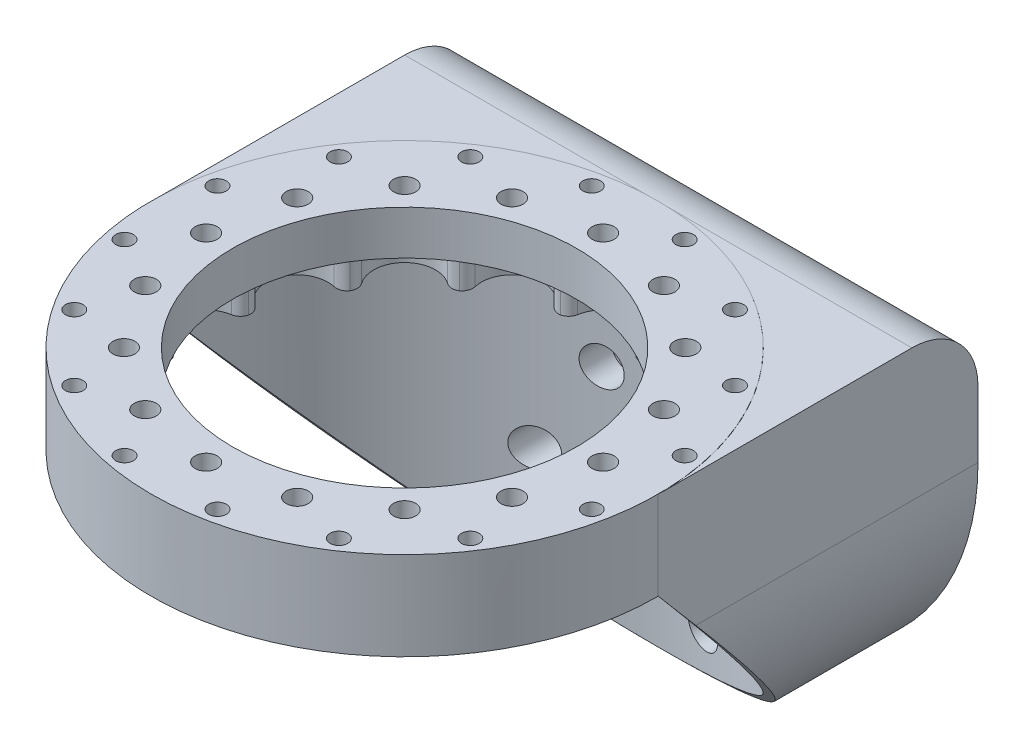
SolidWorks part; units mm, degrees
ref_plane "Front Plane" through (0, 0, 0) normal (0, 0, 1) x (1, 0, 0)
ref_plane "Top Plane" through (0, 0, 0) normal (0, 1, 0) x (1, 0, 0)
ref_plane "Right Plane" through (0, 0, 0) normal (1, 0, 0) x (0, 0, -1)
sketch "Sketch1" plane through (0, 0, 0) normal (0, 1, 0) x (1, 0, 0)
  line L0 (-10.5349, 52.9624) -> (0, 0) construction
  line L1 (0, 0) -> (24.6214, 0) construction
  circle A12 centre (0, 0) radius 39
  circle A13 centre (0, 0) radius 57.5
  circle A14 centre (0, 0) radius 54 construction
  circle A15 centre (-10.5349, 52.9624) radius 2
  circle A16 centre (10.5349, 52.9624) radius 2
  circle A17 centre (30.0008, 44.8994) radius 2
  circle A18 centre (44.8994, 30.0008) radius 2
  circle A19 centre (52.9624, 10.5349) radius 2
  circle A20 centre (52.9624, -10.5349) radius 2
  circle A21 centre (44.8994, -30.0008) radius 2
  circle A22 centre (30.0008, -44.8994) radius 2
  circle A23 centre (10.5349, -52.9624) radius 2
  circle A24 centre (-10.5349, -52.9624) radius 2
  circle A25 centre (-30.0008, -44.8994) radius 2
  circle A26 centre (-44.8994, -30.0008) radius 2
  circle A47 centre (-52.9624, -10.5349) radius 2
  circle A48 centre (-52.9624, 10.5349) radius 2
  circle A49 centre (-44.8994, 30.0008) radius 2
  circle A50 centre (-30.0008, 44.8994) radius 2
  point P21 (0, 0)
  point P28 (0, 0)
  point P56 (0, 0)
  point P60 (0, 0)
  dimension "D1" = 101.25
  dimension "D4" = 115
  dimension "D5" = 78
  dimension "D6" = 108
  dimension "D7" = 4
  dimension "D8" = 16
extrude "Boss-Extrude1" add sketch "Sketch1" along normal blind 10
sketch "Sketch2" plane through (0, 10, 0) normal (0, 1, 0) x (1, 0, 0)
  circle A0 centre (0, 0) radius 45 construction
  circle A1 centre (0, 45) radius 2.5
  circle A2 centre (17.2208, 41.5746) radius 2.5
  circle A3 centre (31.8198, 31.8198) radius 2.5
  circle A4 centre (41.5746, 17.2208) radius 2.5
  circle A5 centre (45, 0) radius 2.5
  circle A6 centre (41.5746, -17.2208) radius 2.5
  circle A7 centre (31.8198, -31.8198) radius 2.5
  circle A8 centre (17.2208, -41.5746) radius 2.5
  circle A9 centre (0, -45) radius 2.5
  circle A10 centre (-17.2208, -41.5746) radius 2.5
  circle A11 centre (-31.8198, -31.8198) radius 2.5
  circle A12 centre (-41.5746, -17.2208) radius 2.5
  circle A13 centre (-45, 0) radius 2.5
  circle A14 centre (-41.5746, 17.2208) radius 2.5
  circle A15 centre (-31.8198, 31.8198) radius 2.5
  circle A16 centre (-17.2208, 41.5746) radius 2.5
  point P27 (0, 0)
  dimension "D1" = 90
  dimension "D2" = 5
  dimension "D3" = 16
extrude "Cut-Extrude1" cut sketch "Sketch2" against normal blind 10
sketch "Sketch4" plane through (0, 0, 0) normal (0, 1, 0) x (1, 0, 0)
  circle A0 centre (0, 0) radius 45 construction
  circle A1 centre (0, 45) radius 5
  circle A2 centre (0, 45) radius 2.5
  circle A3 centre (17.2208, 41.5746) radius 2.5
  circle A4 centre (31.8198, 31.8198) radius 2.5
  circle A5 centre (41.5746, 17.2208) radius 2.5
  circle A6 centre (45, 0) radius 2.5
  circle A7 centre (41.5746, -17.2208) radius 2.5
  circle A8 centre (31.8198, -31.8198) radius 2.5
  circle A9 centre (17.2208, -41.5746) radius 2.5
  circle A10 centre (0, -45) radius 2.5
  circle A11 centre (-17.2208, -41.5746) radius 2.5
  circle A12 centre (-31.8198, -31.8198) radius 2.5
  circle A13 centre (17.2208, 41.5746) radius 5
  circle A14 centre (31.8198, 31.8198) radius 5
  circle A15 centre (41.5746, 17.2208) radius 5
  circle A16 centre (45, 0) radius 5
  circle A17 centre (41.5746, -17.2208) radius 5
  circle A18 centre (31.8198, -31.8198) radius 5
  circle A19 centre (17.2208, -41.5746) radius 5
  circle A20 centre (0, -45) radius 5
  circle A21 centre (-17.2208, -41.5746) radius 5
  circle A22 centre (-31.8198, -31.8198) radius 5
  circle A23 centre (-41.5746, -17.2208) radius 5
  circle A24 centre (-45, 0) radius 5
  circle A25 centre (-41.5746, 17.2208) radius 5
  circle A26 centre (-31.8198, 31.8198) radius 5
  circle A27 centre (-17.2208, 41.5746) radius 5
  circle A28 centre (-41.5746, -17.2208) radius 2.5
  circle A29 centre (-45, 0) radius 2.5
  circle A30 centre (-41.5746, 17.2208) radius 2.5
  circle A31 centre (-31.8198, 31.8198) radius 2.5
  circle A32 centre (-17.2208, 41.5746) radius 2.5
  point P29 (0, 0)
  point P50 (0, 0)
  dimension "D1" = 10
  dimension "D2" = 16
  dimension "D3" = 16
extrude "Boss-Extrude3" add sketch "Sketch4" against normal blind 0.4
sketch "Sketch5" plane through (0, 0, 0) normal (0, -1, 0) x (1, 0, 0)
  circle A0 centre (0, 0) radius 57.5
  circle A1 centre (0, 0) radius 45
  circle A2 centre (0, 45) radius 7
  circle A3 centre (17.2208, 41.5746) radius 7
  circle A4 centre (31.8198, 31.8198) radius 7
  circle A5 centre (41.5746, 17.2208) radius 7
  circle A6 centre (45, 0) radius 7
  circle A7 centre (41.5746, -17.2208) radius 7
  circle A8 centre (31.8198, -31.8198) radius 7
  circle A9 centre (17.2208, -41.5746) radius 7
  circle A10 centre (0, -45) radius 7
  circle A11 centre (-17.2208, -41.5746) radius 7
  circle A12 centre (-31.8198, -31.8198) radius 7
  circle A13 centre (-41.5746, -17.2208) radius 7
  circle A14 centre (-45, 0) radius 7
  circle A15 centre (-41.5746, 17.2208) radius 7
  circle A16 centre (-31.8198, 31.8198) radius 7
  circle A17 centre (-17.2208, 41.5746) radius 7
  circle A18 centre (0, 0) radius 54 construction
  circle A19 centre (-10.5349, 52.9624) radius 2
  circle A20 centre (10.5349, 52.9624) radius 2
  circle A21 centre (30.0008, 44.8994) radius 2
  circle A22 centre (44.8994, 30.0008) radius 2
  circle A23 centre (52.9624, 10.5349) radius 2
  circle A24 centre (52.9624, -10.5349) radius 2
  circle A25 centre (44.8994, -30.0008) radius 2
  circle A26 centre (30.0008, -44.8994) radius 2
  circle A27 centre (10.5349, -52.9624) radius 2
  circle A28 centre (-10.5349, -52.9624) radius 2
  circle A29 centre (-30.0008, -44.8994) radius 2
  circle A30 centre (-44.8994, -30.0008) radius 2
  circle A31 centre (-52.9624, -10.5349) radius 2
  circle A32 centre (-52.9624, 10.5349) radius 2
  circle A33 centre (-44.8994, 30.0008) radius 2
  circle A34 centre (-30.0008, 44.8994) radius 2
  point P39 (0, 0)
  point P75 (0, 0)
  circle M34 centre (0, 0) radius 57.5
  circle M35 centre (-52.9624, 10.5349) radius 2
  circle M37 centre (-52.9624, -10.5349) radius 2
  circle M39 centre (-30.0008, -44.8994) radius 2
  circle M41 centre (10.5349, -52.9624) radius 2
  circle M43 centre (44.8994, -30.0008) radius 2
  circle M45 centre (52.9624, 10.5349) radius 2
  circle M47 centre (30.0008, 44.8994) radius 2
  circle M49 centre (-10.5349, 52.9624) radius 2
  dimension "D1" = 14
  dimension "D2" = 16
  dimension "D3" = 16
extrude "Boss-Extrude4" add sketch "Sketch5" along normal blind 10.06 contours A17 A1 A2 A3 A4 A5 A6 A7 A8 A9 A10 A11 A12 A13 A14 A15 A16 M34 M35 M37 M39 M41 M43 M45 M47 M49 region at (-55.8737, 0, 0)
fillet "Fillet2" radius 2.5 32 edges at (-23.46, -5.03, -38.4009) (-26.5001, -5.03, -36.3696) (-6.9788, -5.03, -44.4556) (-10.5648, -5.03, -43.7422) (10.5648, -5.03, -43.7422) (6.9788, -5.03, -44.4556) (26.5001, -5.03, -36.3696) (23.46, -5.03, -38.4009) (38.4009, -5.03, -23.46) (36.3696, -5.03, -26.5001) (44.4556, -5.03, -6.9788) (43.7422, -5.03, -10.5648) (43.7422, -5.03, 10.5648) (44.4556, -5.03, 6.9788) (-38.4009, -5.03, -23.46) (-36.3696, -5.03, -26.5001) (-44.4556, -5.03, -6.9788) (-43.7422, -5.03, -10.5648) (-43.7422, -5.03, 10.5648) (-44.4556, -5.03, 6.9788) (-36.3696, -5.03, 26.5001) (-38.4009, -5.03, 23.46) (-23.46, -5.03, 38.4009) (-26.5001, -5.03, 36.3696) (-10.5648, -5.03, 43.7422) (-6.9788, -5.03, 44.4556) (6.9788, -5.03, 44.4556) (10.5648, -5.03, 43.7422) (23.46, -5.03, 38.4009) (26.5001, -5.03, 36.3696) (38.4009, -5.03, 23.46) (36.3696, -5.03, 26.5001)
sketch "Sketch6" plane through (0, -10.06, 0) normal (0, -1, 0) x (1, 0, 0)
  line L0 (-57.5, 0) -> (57.5, 0) construction
  line L1 (57.5, 0) -> (57.5, -57.5)
  line L2 (57.5, -57.5) -> (-57.5, -57.5)
  line L3 (-57.5, -57.5) -> (-57.5, 0)
  circle A0 centre (0, 0) radius 57.5 construction
  arc A1 (-57.5, 0) -> (57.5, 0) centre (0, 0) ccw
extrude "Boss-Extrude7" add sketch "Sketch6" against normal blind 20 contours A1 L2 L1 | A1 L3 L2 region at (-44.6563, -10.06, -44.6563) region at (44.6563, -10.06, -44.6563)
sketch "Sketch7" plane through (-57.5, 0, 0) normal (-1, 0, 0) x (0, 0, 1)
  line L0 (-57.5, 9.94) -> (-57.5, -77.56)
  line L1 (-57.5, -77.56) -> (-72.5, -77.56)
  line L2 (-72.5, -77.56) -> (-72.5, 9.94)
  line L3 (-72.5, 9.94) -> (-57.5, 9.94)
  line L4 (-57.5, -77.56) -> (0, -10.06)
  line L5 (0, -10.06) -> (-57.5, -10.06)
  line M5 (-57.5, -10.06) -> (0, -10.06)
  line M8 (-57.5, 9.94) -> (-57.5, -10.06)
  dimension "D1" = 15
  dimension "D2" = 87.5
  dimension "D3" = 67.5
extrude "Boss-Extrude8" add sketch "Sketch7" against normal blind 115 contours L3 L2 L1 L0 M8 | L0 L4 M5 region at (-57.5, -33.81, -65) region at (-57.5, -32.56, -38.3333)
sketch "Sketch8" plane through (0, -77.56, 0) normal (0, -1, 0) x (1, 0, 0)
  circle A0 centre (0, 0) radius 57.5
extrude "Cut-Extrude2" cut sketch "Sketch8" against normal blind 67.5
sketch "Sketch9" plane through (0, 0, -72.5) normal (0, 0, -1) x (-1, 0, 0)
  line L0 (0, 19.2611) -> (0, -105.8991) construction
  line L1 (-57.5, -77.56) -> (57.5, -77.56) construction
  circle A0 centre (0, -47.56) radius 30 construction
  circle A1 centre (0, -47.56) radius 23 construction
  circle A2 centre (23, -47.56) radius 2
  circle A3 centre (11.5, -67.4786) radius 2
  circle A4 centre (-11.5, -67.4786) radius 2
  circle A5 centre (-23, -47.56) radius 2
  circle A6 centre (-11.5, -27.6414) radius 2
  circle A7 centre (11.5, -27.6414) radius 2
  point P22 (0, -47.56)
  dimension "D1" = 60
  dimension "D2" = 46
  dimension "D3" = 4
  dimension "D4" = 6
extrude "Cut-Extrude3" cut sketch "Sketch9" against normal blind 67.5
sketch "Sketch10" plane through (0, 0, 0) normal (0, 0, 1) x (1, 0, 0)
  line L0 (57.5, -77.56) -> (0, -77.56) construction
  circle A0 centre (0, -47.56) radius 30 construction
  circle A1 centre (0, -47.56) radius 23 construction
  circle A2 centre (23, -47.56) radius 4.25
  circle A3 centre (11.5, -67.4786) radius 4.25
  circle A4 centre (-11.5, -67.4786) radius 4.25
  circle A5 centre (-23, -47.56) radius 4.25
  circle A6 centre (-11.5, -27.6414) radius 4.25
  circle A7 centre (11.5, -27.6414) radius 4.25
  point P19 (0, -47.56)
  dimension "D1" = 60
  dimension "D2" = 46
  dimension "D3" = 8.5
  dimension "D4" = 6
extrude "Cut-Extrude4" cut sketch "Sketch10" against normal blind 62.5
sketch "Sketch11" plane through (0, 0, -72.5) normal (0, 0, -1) x (-1, 0, 0)
  line L0 (0, 13.9005) -> (0, -82.4311) construction
  line L1 (-57.5, -77.56) -> (57.5, -77.56) construction
  line L2 (-57.5, -20.06) -> (-57.5, -77.56)
  line L3 (-57.5, -77.56) -> (57.5, -77.56)
  line L4 (57.5, -77.56) -> (57.5, -20.06)
  circle A0 centre (0, -20.06) radius 57.5
  line M8 (57.5, -77.56) -> (57.5, 9.94)
  line M10 (-57.5, 9.94) -> (-57.5, -77.56)
  line M11 (-57.5, -77.56) -> (57.5, -77.56)
  dimension "D1" = 115
extrude "Cut-Extrude5" cut sketch "Sketch11" against normal blind 133 contours A0 M10 M11 | A0 L3 M8 region at (44.6563, -64.7163, -72.5) region at (-44.6563, -64.7163, -72.5)
fillet "Fillet4" radius 15 1 edges at (0, 9.94, -72.5)
